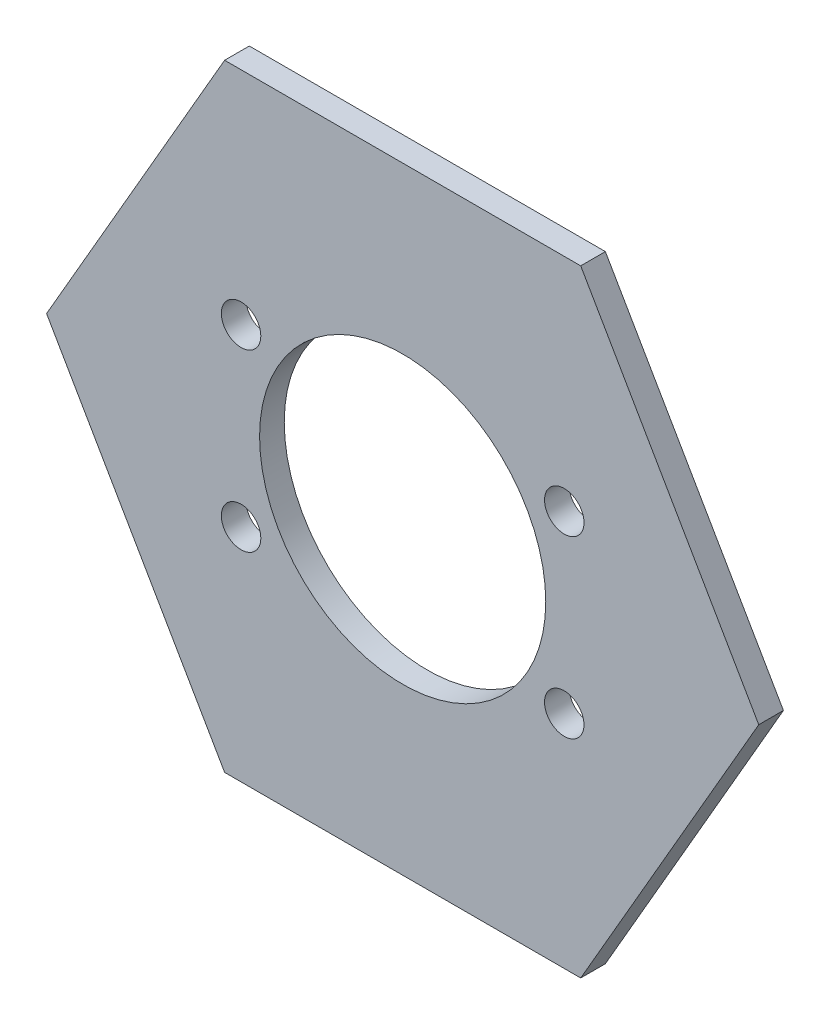
SolidWorks part; units mm, degrees
ref_plane "Front Plane" through (0, 0, 0) normal (0, 0, 1) x (1, 0, 0)
ref_plane "Top Plane" through (0, 0, 0) normal (0, 1, 0) x (1, 0, 0)
ref_plane "Right Plane" through (0, 0, 0) normal (1, 0, 0) x (0, 0, -1)
sketch "Sketch1" plane through (0, 0, 0) normal (0, 0, 1) x (1, 0, 0)
  line L0 (0, 0) -> (0, -25) construction
  line L1 (-8.5, -17.5) -> (8.5, -17.5) construction
  line L2 (-14.4338, 25) -> (14.4338, 25)
  line L3 (-5, -19) -> (5, -19) construction
  line L4 (-5, -19) -> (-5, -24) construction
  line L5 (-5, -24) -> (5, -24) construction
  line L6 (5, -19) -> (5, -24) construction
  line L7 (14.4338, 25) -> (28.8675, 0)
  line L8 (28.8675, 0) -> (14.4338, -25)
  line L9 (14.4338, -25) -> (-14.4338, -25)
  line L10 (-14.4338, -25) -> (-28.8675, 0)
  line L11 (-28.8675, 0) -> (-14.4338, 25)
  circle A0 centre (0, 0) radius 8 construction
  circle A1 centre (0, 0) radius 11.6
  circle A2 centre (0, 0) radius 11.1 construction
  circle A3 centre (0, 0) radius 11.1 construction
  circle A6 centre (-13.1, -7.1) radius 1.6
  circle A7 centre (-13.1, 7.1) radius 1.6
  circle A8 centre (13.1, 7.1) radius 1.6
  circle A9 centre (13.1, -7.1) radius 1.6
  circle A10 centre (0, 0) radius 25 construction
  circle A11 centre (-13.1, -7.1) radius 1.6 construction
  circle A12 centre (-13.1, 7.1) radius 1.6 construction
  circle A13 centre (13.1, 7.1) radius 1.6 construction
  circle A14 centre (13.1, -7.1) radius 1.6 construction
  dimension "D2" = 50
  dimension "D1" = 0.5
  dimension "D3" = 5
  dimension "D4" = 10
  dimension "D5" = 1
extrude "Boss-Extrude1" add sketch "Sketch1" along normal blind 2
